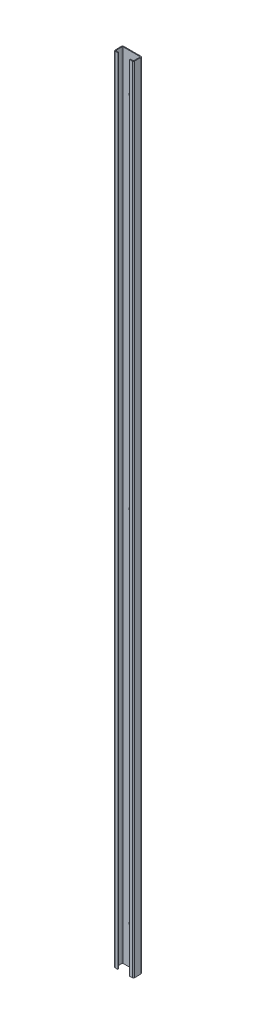
SolidWorks part; units mm, degrees
note: '?' marks a value the reader was unsure of. The reader was unsure of these and kept them because the rebuilt part matched: thickness of "Base-Flange1", "Edge-Flange1", "Edge-Flange2", "Sheet-Metal1", "Sheet-Metal2", "Sheet-Metal3", "Sheet-Metal6"; flange length of "Edge-Flange1", "Edge-Flange2".
ref_plane "Front Plane" through (0, 0, 0) normal (0, 0, 1) x (1, 0, 0)
ref_plane "Top Plane" through (0, 0, 0) normal (0, 1, 0) x (1, 0, 0)
ref_plane "Right Plane" through (0, 0, 0) normal (1, 0, 0) x (0, 0, -1)
sketch "BaseFlange" plane through (0, 0, 0) normal (0, 0, 1) x (1, 0, 0)
  line L1 (25, 1023.5) -> (-25, 1023.5)
  line L2 (25, 1023.5) -> (25, -1023.5)
  line L3 (25, -1023.5) -> (-25, -1023.5)
  line L4 (-25, 1023.5) -> (-25, -1023.5)
  line L5 (25, 1023.5) -> (-25, -1023.5) construction
  line L6 (25, -1023.5) -> (-25, 1023.5) construction
  point P0 (0, 0)
  dimension "D1" = 50
  dimension "Height" = 2047
base flange "Base-Flange1" sketch "BaseFlange" thickness 2 reverse thickness direction yes parameters "D1"=1
edge flange "Edge-Flange1" sketch "Sketch10" flange profiles "Sketch10", "Sketch11" flange angle 90 flange length 22 flange position material inside bend radius 1 thickness 2 relief rectangular parameters "D6"=10, "D8"=1
sketch "Sketch10" plane through (25, 0, 2) normal (-1, 0, 0) x (0, -1, 0)
  line L1 (-1023.5, 0) -> (1023.5, 0) construction
  line L2 (1023.5, 0) -> (1023.5, 20)
  line L3 (1023.5, 20) -> (-1023.5, 20)
  line L4 (-1023.5, 20) -> (-1023.5, 0)
  line L5 (-1023.5, 0) -> (1023.5, 0)
sketch "Sketch11" plane through (-25, 0, 2) normal (1, 0, 0) x (0, 1, 0)
  line L0 (-1023.5, 0) -> (1023.5, 0) construction
  line L1 (-1023.5, 0) -> (1023.5, 0)
  line L2 (-1023.5, 0) -> (-1023.5, 20)
  line L3 (-1023.5, 20) -> (1023.5, 20)
  line L4 (1023.5, 20) -> (1023.5, 0)
bend "EdgeBend1" bend radius 1 bend angle 90 parameters "D5"=1
bend "EdgeBend2" bend radius 1 bend angle 90 parameters "D5"=2
edge flange "Edge-Flange2" sketch "Sketch16" flange profiles "Sketch16", "Sketch17" flange angle 90 flange length 10 flange position material inside bend radius 1 thickness 2 relief rectangular parameters "D6"=10, "D8"=1
sketch "Sketch16" plane through (-23, 0, 22) normal (0, 0, 1) x (0, -1, 0)
  line L2 (1023.5, 0) -> (1023.5, 8)
  line L3 (1023.5, 8) -> (-1023.5, 8)
  line L4 (-1023.5, 8) -> (-1023.5, 0)
  line L5 (1023.5, 0) -> (-1023.5, 0) construction
  line L6 (1023.5, 0) -> (-1023.5, 0)
sketch "Sketch17" plane through (23, 0, 22) normal (0, 0, 1) x (0, 1, 0)
  line L0 (1023.5, 0) -> (-1023.5, 0) construction
  line L1 (1023.5, 0) -> (-1023.5, 0)
  line L2 (1023.5, 0) -> (1023.5, 8)
  line L3 (1023.5, 8) -> (-1023.5, 8)
  line L4 (-1023.5, 8) -> (-1023.5, 0)
bend "EdgeBend3" bend radius 1 bend angle 90 parameters "D5"=3
bend "EdgeBend4" bend radius 1 bend angle 90 parameters "D5"=4
sketch "HingeHoles" plane through (0, 0, 0) normal (0, 0, 1) x (1, 0, 0)
  line L0 (-22, -1023.5) -> (22, -1023.5) construction
  line L1 (22, 1023.5) -> (-22, 1023.5) construction
  line L2 (-25, -1023.5) -> (-25, 1023.5) construction
  circle A0 centre (-2, 925.5) radius 4.6
  circle A1 centre (-2, 0) radius 4.6
  circle A2 centre (-2, -925.5) radius 4.6
  dimension "D1" = 98
  dimension "D2" = 98
  dimension "D3" = 9.2
  dimension "HingeHole" = 23
extrude "Cut-Extrude1" cut sketch "HingeHoles" along normal through all normal cut yes
ref_axis "Axis1" through (-2, 925.5, 2) along (0, 0, -1)?
sketch "Bend-Lines1" [suppressed] plane through (0, 0, 0) normal (0, 1, 0) x (1, 0, 0)
sketch "Bounding-Box1" [suppressed] plane through (0, 0, 0) normal (0, 1, 0) x (1, 0, 0)
sheet metal parameters "Sheet-Metal1" thickness 2 parameters "D1"=1
flat pattern "Flat-Pattern1" [suppressed]
sketch "Bend-Lines2" plane through (0, 0, 0) normal (0, 1, 0) x (1, 0, 0)
sketch3d "Bounding-Box2" [suppressed]
  line L0 (-40, 950, 0) -> (-40, -950, 0) construction
  line L1 (40, 950, 0) -> (40, -950, 0) construction
  line L2 (-40, 950, 0) -> (40, 950, 0) construction
  line L3 (-40, -950, 0) -> (40, -950, 0) construction
sheet metal parameters "Sheet-Metal2" thickness 2 parameters "D1"=1
flat pattern "Flat-Pattern1"
sketch "Bend-Lines2" plane through (0, 0, 0) normal (0, 0, 1) x (1, 0, 0)
  line L0 (-23.2017, 947.5) -> (-23.2017, -947.5) construction
  line L1 (23.2017, -947.5) -> (23.2017, 947.5) construction
  line L2 (-23.2017, 947.5) -> (-23.2017, -947.5) construction
  line L3 (23.2017, -947.5) -> (23.2017, 947.5) construction
sketch3d "Bounding-Box2" [suppressed]
  line L0 (46.4033, 947.5, 0) -> (46.4033, -947.5, 0) construction
  line L1 (-46.4033, 947.5, 0) -> (-46.4033, -947.5, 0) construction
  line L2 (46.4033, 947.5, 0) -> (-46.4033, 947.5, 0) construction
  line L3 (46.4033, -947.5, 0) -> (-46.4033, -947.5, 0) construction
bend of the flat pattern "Flatten-<EdgeBend1>1"
bend of the flat pattern "Flatten-<EdgeBend2>1"
sheet metal parameters "Sheet-Metal3" thickness 2 parameters "D1"=1
flat pattern "Flat-Pattern1"
sketch "Bend-Lines2" plane through (0, 0, 0) normal (0, 0, -1) x (-1, 0, 0)
  line L0 (23.2017, -1023.5) -> (23.2017, 1023.5) construction
  line L1 (-23.2017, 1023.5) -> (-23.2017, -1023.5) construction
  line L2 (23.2017, -1023.5) -> (23.2017, 1023.5) construction
  line L3 (-23.2017, 1023.5) -> (-23.2017, -1023.5) construction
  line L4 (-41.605, 1023.5) -> (-41.605, -1023.5) construction
  line L5 (41.605, -1023.5) -> (41.605, 1023.5) construction
  line L6 (-41.605, 1023.5) -> (-41.605, -1023.5) construction
  line L7 (41.605, -1023.5) -> (41.605, 1023.5) construction
sketch3d "Bounding-Box2" [suppressed]
  line L0 (-49.8066, 1023.5, 0) -> (-49.8066, -1023.5, 0) construction
  line L1 (49.8066, 1023.5, 0) -> (49.8066, -1023.5, 0) construction
  line L2 (-49.8066, 1023.5, 0) -> (49.8066, 1023.5, 0) construction
  line L3 (-49.8066, -1023.5, 0) -> (49.8066, -1023.5, 0) construction
bend of the flat pattern "Flatten-<EdgeBend1>1"
bend of the flat pattern "Flatten-<EdgeBend2>1"
bend of the flat pattern "Flatten-<EdgeBend3>1"
bend of the flat pattern "Flatten-<EdgeBend4>1"
sheet metal parameters "Sheet-Metal6" thickness 2 parameters "D1"=1
flat pattern "Flat-Pattern1"
sketch "Bend-Lines2" plane through (0, 0, 0) normal (0, 0, -1) x (-1, 0, 0)
  line L0 (23.2017, -1023.5) -> (23.2017, 1023.5) construction
  line L1 (-23.2017, 1023.5) -> (-23.2017, -1023.5) construction
  line L2 (23.2017, -1023.5) -> (23.2017, 1023.5) construction
  line L3 (-23.2017, 1023.5) -> (-23.2017, -1023.5) construction
  line L4 (-41.605, 1023.5) -> (-41.605, -1023.5) construction
  line L5 (41.605, -1023.5) -> (41.605, 1023.5) construction
  line L6 (-41.605, 1023.5) -> (-41.605, -1023.5) construction
  line L7 (41.605, -1023.5) -> (41.605, 1023.5) construction
sketch3d "Bounding-Box2" [suppressed]
  line L0 (-49.8066, 1023.5, 0) -> (-49.8066, -1023.5, 0) construction
  line L1 (49.8066, 1023.5, 0) -> (49.8066, -1023.5, 0) construction
  line L2 (-49.8066, 1023.5, 0) -> (49.8066, 1023.5, 0) construction
  line L3 (-49.8066, -1023.5, 0) -> (49.8066, -1023.5, 0) construction
bend of the flat pattern "Flatten-<EdgeBend1>1"
bend of the flat pattern "Flatten-<EdgeBend2>1"
bend of the flat pattern "Flatten-<EdgeBend3>1"
bend of the flat pattern "Flatten-<EdgeBend4>1"
